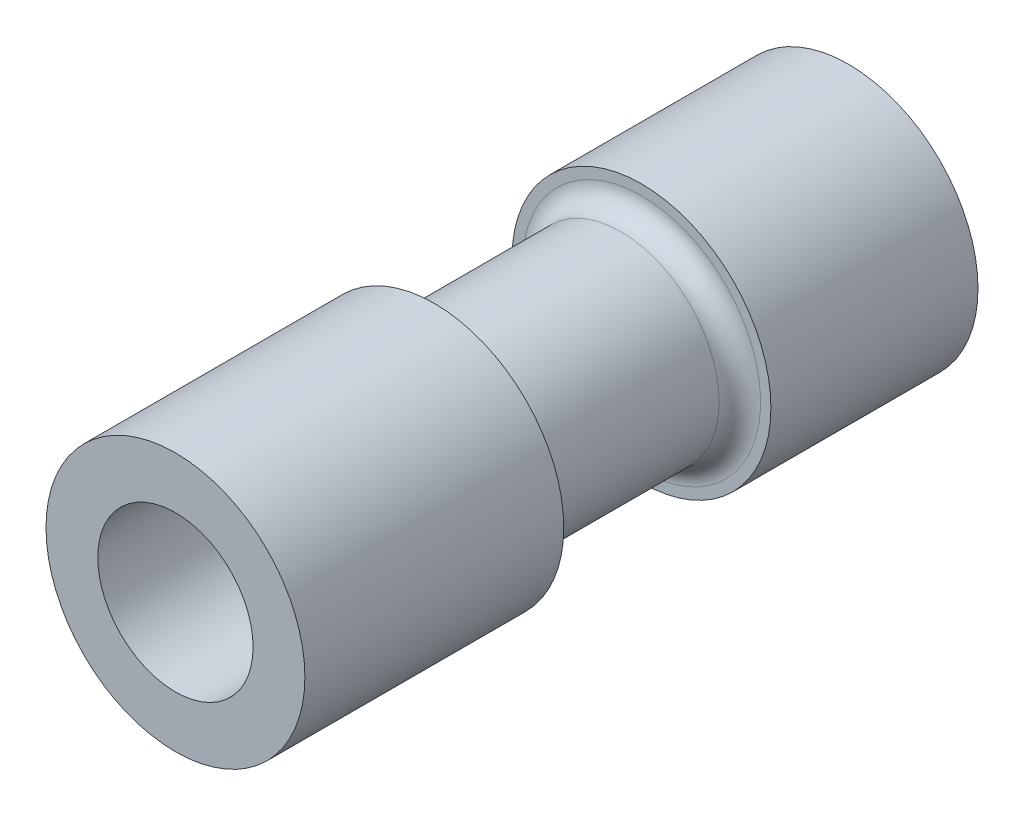
SolidWorks part; units mm, degrees
ref_plane "Front Plane" through (0, 0, 0) normal (0, 0, 1) x (1, 0, 0)
ref_plane "Top Plane" through (0, 0, 0) normal (0, 1, 0) x (1, 0, 0)
ref_plane "Right Plane" through (0, 0, 0) normal (1, 0, 0) x (0, 0, -1)
sketch "Sketch1" plane through (0, 0, 0) normal (0, 0, 1) x (1, 0, 0)
  circle A0 centre (0, 0) radius 2.5
  dimension "D1" = 5
extrude "Boss-Extrude1" add sketch "Sketch1" along normal blind 13
cosmetic thread "Cosmetic Thread2" parameters "D1"=13, "D2"=4.11
sketch "Sketch3" plane through (0, 0, 0) normal (0, 1, 0) x (1, 0, 0)
  line L1 (3.1382, -4) -> (2.3, -4)
  line L2 (3.1382, -4) -> (3.1382, -8)
  line L3 (3.1382, -8) -> (2.3, -8)
  line L4 (1.9, -4.4) -> (1.9, -7.6)
  line L7 (0, 0) -> (0, -16.2401) construction
  line L8 (2.5, 0) -> (-2.5, 0) construction
  arc A0 (1.9, -7.6) -> (2.3, -8) centre (2.3, -7.6) ccw
  arc A1 (2.3, -4) -> (1.9, -4.4) centre (2.3, -4.4) ccw
  dimension "D4" = 0.4
  dimension "D1" = 1.9
  dimension "D2" = 4
  dimension "D3" = 4
revolve "Cut-Revolve1" cut sketch "Sketch3" angle 360 about L7
hole_wizard "Ø2.0 (2) Diameter Hole1" positions "Sketch5" profile "Sketch4" hole size "Ø2.0" standard "Ansi Metric" end condition through all
sketch "Sketch5" plane through (0, 0, 13) normal (0, 0, 1) x (1, 0, 0)
  point P0 (0, 0)
sketch "Sketch4" plane through (0, 0, 13) normal (1, 0, 0) x (0, -1, 0)
  line L0 (0, 0) -> (0, 13)
  line L1 (0, 13) -> (1, 13)
  line L2 (1, 13) -> (1, 0)
  line L5 (1, 0) -> (0, 0)
  line L11 (0, -6.35) -> (0, 107.95) construction
  dimension "Thru Hole Dia." = 2
  dimension "Thru Hole Depth" = 13
sketch "Sketch6" plane through (0, 0, 0) normal (0, 0, -1) x (-1, 0, 0)
  circle A0 centre (0, 0) radius 0.25
  dimension "D1" = 0.5
sketch "Sketch8" plane through (0, 0, 13) normal (0, 0, 1) x (1, 0, 0)
  circle A0 centre (0, 0) radius 1.5
  dimension "D1" = 3
extrude "Cut-Extrude1" cut sketch "Sketch8" against normal blind 8
